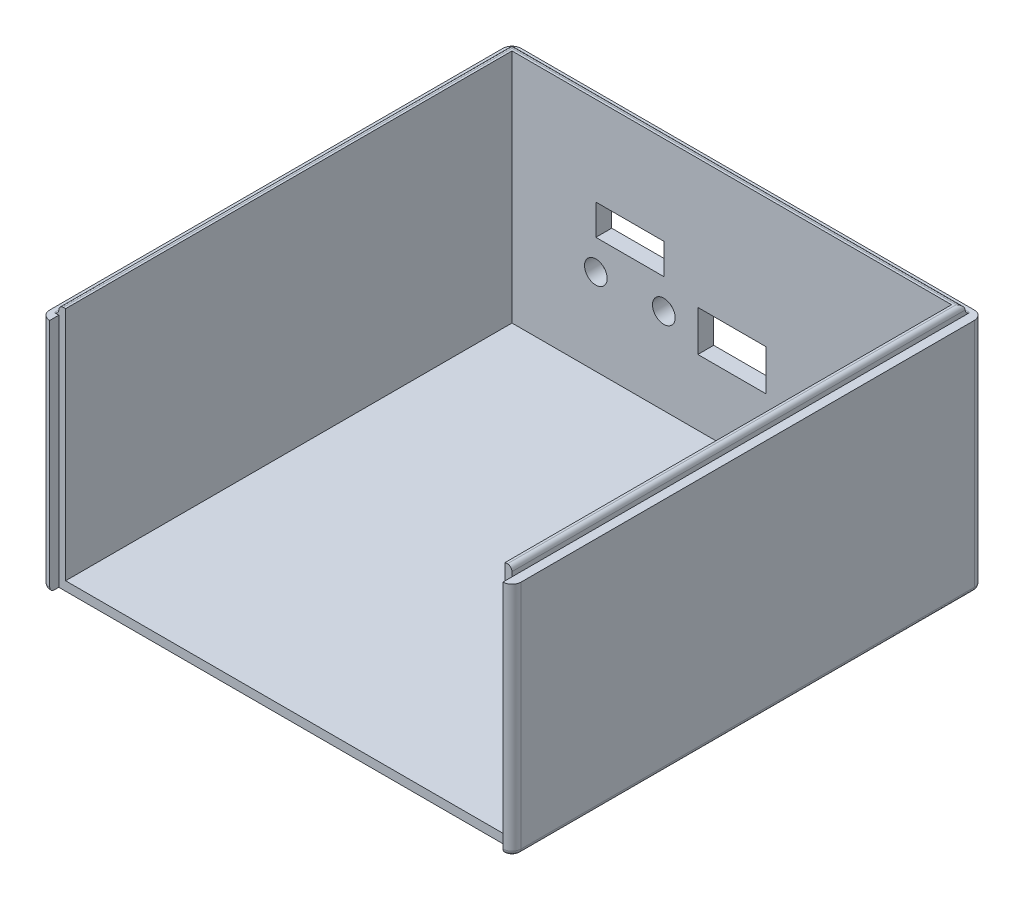
SolidWorks part; units mm, degrees
ref_plane "Piano frontale" through (0, 0, 0) normal (0, 0, 1) x (1, 0, 0)
ref_plane "Piano superiore" through (0, 0, 0) normal (0, 1, 0) x (1, 0, 0)
ref_plane "Piano destro" through (0, 0, 0) normal (1, 0, 0) x (0, 0, -1)
sketch "Schizzo1" plane through (0, 0, 0) normal (0, 1, 0) x (1, 0, 0)
  line L0 (-50, -50) -> (-50, -52)
  line L1 (50, -50) -> (-50, -50)
  line L2 (50, -50) -> (50, 50)
  line L3 (50, 50) -> (-50, 50)
  line L4 (-50, -50) -> (-50, 50)
  line L5 (50, -50) -> (-50, 50) construction
  line L6 (50, 50) -> (-50, -50) construction
  line L7 (-50, -52) -> (-52, -52)
  line L8 (-52, -52) -> (-52, 52)
  line L9 (-52, 52) -> (52, 52)
  line L10 (52, 52) -> (52, -52)
  line L11 (52, -52) -> (50, -52)
  line L12 (50, -52) -> (50, -50)
  point P0 (0, 0)
  dimension "D1" = 100
  dimension "D2" = 100
  dimension "D3" = 2
  dimension "D4" = 2
  dimension "D5" = 104
  dimension "D6" = 104
extrude "Estrusione-Estrusione1" add sketch "Schizzo1" along normal blind 2 contours L2 L1 L4 L3
sketch "Schizzo2" plane through (0, 0, 0) normal (0, 1, 0) x (1, 0, 0)
  line L0 (-50, -50) -> (-50, -52)
  line L1 (-50, -52) -> (-52, -52)
  line L2 (-52, -52) -> (-52, 52)
  line L3 (-52, 52) -> (52, 52)
  line L4 (52, 52) -> (52, -52)
  line L5 (52, -52) -> (49.9972, -52)
  line L6 (49.9972, -52) -> (49.9972, -50)
  line L7 (50, -50) -> (-50, -50) construction
  line L8 (49.9972, -50) -> (50, 50)
  line L9 (50, 50) -> (-50, 50)
  line L10 (50, 50) -> (-50, 50) construction
  line L11 (-50, 50) -> (-50, -50)
  dimension "D1" = 2
  dimension "D2" = 2
  dimension "D3" = 104
  dimension "D4" = 104
extrude "Estrusione-Estrusione2" add sketch "Schizzo2" along normal blind 52
sketch "Schizzo3" plane through (0, 0, 0) normal (0, 1, 0) x (1, 0, 0)
  line L0 (-50, -50) -> (-50, 50)
  line L1 (-50, 50) -> (50, 50)
  line L2 (50, 50) -> (49.9972, -50)
  line L3 (49.9972, -50) -> (48.4972, -50)
  line L4 (49.9972, -50) -> (-50, -50) construction
  line L5 (48.4972, -50) -> (48.4972, 48.5)
  line L6 (48.4972, 48.5) -> (-48.5028, 48.5)
  line L7 (-48.5028, 48.5) -> (-48.5028, -50)
  line L8 (-48.5028, -50) -> (-50, -50)
  dimension "D1" = 1.5
  dimension "D2" = 98.5
  dimension "D3" = 97
extrude "Estrusione-Estrusione3" add sketch "Schizzo3" along normal blind 54
fillet "Raccordo1" radius 1 3 edges at (49.9986, 54, 0) (0, 54, -50) (-50, 54, 0)
fillet "Raccordo2" radius 1 2 edges at (-50, 52, 0) (0, 52, -50)
fillet "Raccordo3" radius 2 3 edges at (52, 26, -52) (52, 26, 52) (-52, 26, 52)
fillet "Raccordo4" radius 2 1 edges at (-52, 26, -52)
fillet "Raccordo5" radius 1 8 edges at (49.9986, 0, 52) (52, 0, 0) (0, 0, -52) (-52, 0, 0) (51.4142, 0, 51.4142) (51.4142, 0, -51.4142) (-51.4142, 0, -51.4142) (-51.4142, 0, 51.4142)
sketch "Schizzo4" plane through (0, 0, -52) normal (0, 0, -1) x (-1, 0, 0)
  line L1 (-50, 1) -> (50, 1) construction
  line L2 (50, 1) -> (50, 52) construction
  line L3 (30.0027, 27.6254) -> (15, 27.6254)
  line L4 (30.0027, 27.6254) -> (30.0027, 34.3746)
  line L5 (30.0027, 34.3746) -> (15, 34.3746)
  line L6 (15, 27.6254) -> (15, 34.3746)
  line L7 (30.0027, 27.6254) -> (15, 34.3746) construction
  line L8 (30.0027, 34.3746) -> (15, 27.6254) construction
  line L9 (7.4966, 25.5) -> (-7.5034, 25.5)
  line L10 (7.4966, 25.5) -> (7.4966, 16.5)
  line L11 (7.4966, 16.5) -> (-7.5034, 16.5)
  line L12 (-7.5034, 25.5) -> (-7.5034, 16.5)
  line L13 (7.4966, 25.5) -> (-7.5034, 16.5) construction
  line L14 (7.4966, 16.5) -> (-7.5034, 25.5) construction
  circle A2 centre (30.0013, 21) radius 2.5
  circle A3 centre (15, 21) radius 2.5
  point P0 (30.0013, 21)
  point P3 (50, 21)
  point P4 (15, 21)
  point P5 (30, 1)
  point P6 (15, 1)
  point P13 (30.0013, 31)
  point P14 (15, 31)
  point P15 (22.5013, 31)
  point P16 (22.5013, 31)
  point P22 (0, 1)
  point P23 (-0.0034, 21)
  point P24 (-0.0034, 21)
  point P29 (0, 1)
  point P30 (0, 1)
  point P31 (0, 21.0938)
  dimension "D5" = 15
  dimension "D3" = 10
  dimension "D1" = 20
  dimension "D2" = 20
  dimension "D4" = 7.5
  dimension "D6" = 9
  dimension "D7" = 20
extrude "Taglio-Estrusione1" cut sketch "Schizzo4" against normal blind 10 contours A3 | A2 | L6 L3 L4 L5 | L10 L9 L12 L11 region at (-22.5013, 31, -52) region at (-30.0013, 21, -52) region at (-15, 21, -52)
